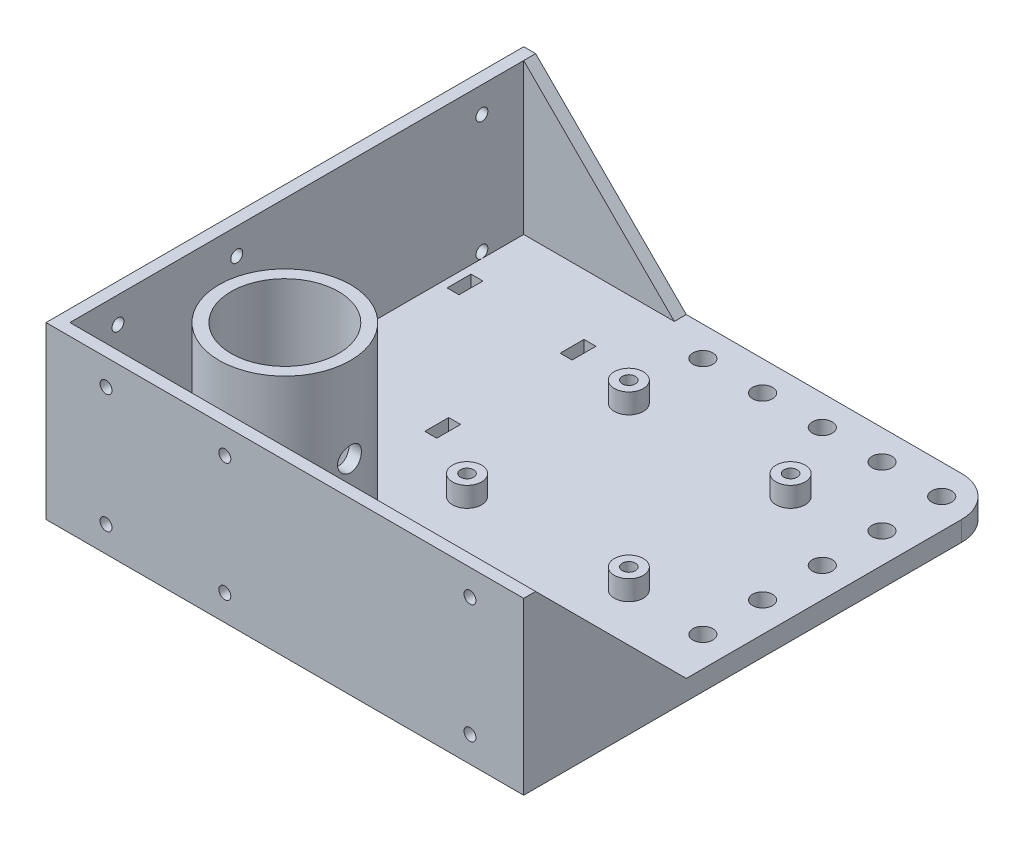
SolidWorks part; units mm, degrees
ref_plane "Front Plane" through (0, 0, 0) normal (0, 0, 1) x (1, 0, 0)
ref_plane "Top Plane" through (0, 0, 0) normal (0, 1, 0) x (1, 0, 0)
ref_plane "Right Plane" through (0, 0, 0) normal (1, 0, 0) x (0, 0, -1)
sketch "Sketch1" plane through (0, 0, 0) normal (0, 1, 0) x (1, 0, 0)
  line L0 (-30, -30) -> (90, 90) construction
  line L1 (-30, -30) -> (90, -30)
  line L2 (-30, -30) -> (-30, 90)
  line L3 (-30, 90) -> (90, 90)
  line L4 (90, -30) -> (90, 90)
  dimension "D1" = 120
  dimension "D2" = 30
extrude "Boss-Extrude1" add sketch "Sketch1" against normal blind 5
sketch "Sketch2" plane through (0, 0, 0) normal (0, 1, 0) x (1, 0, 0)
  line L0 (-30, 90) -> (-27, 90)
  line L1 (90, 90) -> (-30, 90) construction
  line L2 (-27, 90) -> (-27, -27)
  line L3 (-27, -27) -> (90, -27)
  line L4 (90, -30) -> (90, 90) construction
  line L5 (90, -27) -> (90, -30)
  line L6 (90, -30) -> (-30, -30)
  line L7 (-30, -30) -> (-30, 90)
  dimension "D1" = 3
extrude "Boss-Extrude2" add sketch "Sketch2" along normal blind 42.84 from surface starting at face at (30, -5, -30)
sketch "Sketch6" plane through (0, 0, 30) normal (0, 0, 1) x (1, 0, 0)
  line L0 (-14.92, 31.34) -> (14.92, 1.5) construction
  line L1 (14.92, 31.34) -> (-14.92, 1.5) construction
  line L2 (-30, -5) -> (-30, 37.84) construction
  line L3 (90, 37.84) -> (-30, 37.84) construction
  circle A0 centre (-14.92, 31.34) radius 1.5
  circle A1 centre (14.92, 31.34) radius 1.5
  circle A2 centre (14.92, 1.5) radius 1.5
  circle A3 centre (-14.92, 1.5) radius 1.5
  circle A4 centre (76.5, 31.34) radius 1.5
  circle A5 centre (76.5, 1.5) radius 1.5
  point P4 (0, 16.42)
  point P8 (-30, 16.42)
  dimension "D3" = 3
  dimension "D1" = 42.2
  dimension "D2" = 45
  dimension "D4" = 61.58
extrude "Cut-Extrude1" cut sketch "Sketch6" against normal through all
ref_plane "Plane1" through (0, 0, 0) normal (-0.7071, 0, -0.7071) x (-0.7071, 0, 0.7071)
mirror "Mirror1" about plane through (0, 0, 0) normal (-0.7071, 0, -0.7071) of "Cut-Extrude1"
sketch "Sketch3" plane through (90, 0, 0) normal (1, 0, 0) x (0, 0, -1)
  line L0 (-27, 37.84) -> (-27, 0)
  line L1 (-27, 0) -> (10.84, 0)
  line L2 (-27, 0) -> (90, 0) construction
  line L3 (10.84, 0) -> (-27, 37.84)
extrude "Boss-Extrude3" add sketch "Sketch3" against normal blind 3
sketch "Sketch7" plane through (0, 0, 0) normal (0, 1, 0) x (1, 0, 0)
  circle A0 centre (0, 0) radius 13.5
  dimension "D1" = 27
extrude "Cut-Extrude2" cut sketch "Sketch7" against normal through all
sketch "Sketch8" plane through (0, 0, 0) normal (0, 1, 0) x (1, 0, 0)
  circle A0 centre (0, 0) radius 13.5 construction
  circle A1 centre (0, 0) radius 13.5
  circle A2 centre (0, 0) radius 16.5
  dimension "D1" = 3
extrude "Boss-Extrude5" add sketch "Sketch8" along normal through all
sketch "Sketch9" plane through (0, 0, 0) normal (1, 0, 0) x (0, 0, -1)
  line L0 (0, 37.84) -> (0, -5) construction
  line L1 (13.5, 37.84) -> (-13.5, 37.84) construction
  line L2 (-30, -5) -> (90, -5) construction
  circle A0 centre (0, 16.42) radius 3
  dimension "D1" = 6
extrude "Cut-Extrude3" cut sketch "Sketch9" along normal through all
sketch "Sketch10" plane through (0, 0, 0) normal (0, 1, 0) x (1, 0, 0)
  line L0 (37.75, 3.4) -> (65.75, -22) construction
  line L5 (31.75, 3.4) -> (37.75, 3.4)
  line L6 (31.75, 3.4) -> (31.75, 6.4)
  line L7 (31.75, 6.4) -> (37.75, 6.4)
  line L8 (37.75, 3.4) -> (37.75, 6.4)
  line L9 (71.75, 3.4) -> (65.75, 3.4)
  line L10 (71.75, 3.4) -> (71.75, 6.4)
  line L11 (71.75, 6.4) -> (65.75, 6.4)
  line L12 (65.75, 3.4) -> (65.75, 6.4)
  line L13 (71.75, -22) -> (65.75, -22)
  line L14 (71.75, -22) -> (71.75, -25)
  line L15 (71.75, -25) -> (65.75, -25)
  line L16 (65.75, -22) -> (65.75, -25)
  line L17 (31.75, -22) -> (37.75, -22)
  line L18 (31.75, -22) -> (31.75, -25)
  line L19 (31.75, -25) -> (37.75, -25)
  line L20 (37.75, -22) -> (37.75, -25)
  line L21 (21.75, 3.4) -> (81.75, 3.4) construction
  line L22 (21.75, 3.4) -> (21.75, -22) construction
  line L23 (21.75, -22) -> (81.75, -22) construction
  line L24 (81.75, 3.4) -> (81.75, -22) construction
  line L25 (-27, -27) -> (87, -27) construction
  line L27 (16.5, 0) -> (21.75, 0) construction
  line L28 (81.75, -9.3) -> (87, -9.3) construction
  line L29 (87, 10.84) -> (87, -27) construction
  line L30 (90, 90) -> (-30, -30) construction
  line L31 (90, 10.84) -> (90, 90) construction
  circle A0 centre (0, 0) radius 16.5 construction
  circle A1 centre (0, 0) radius 16.5 construction
  circle A2 centre (82.5, 82.5) radius 2.5
  circle A3 centre (82.5, 67.5) radius 2.5
  circle A4 centre (82.5, 52.5) radius 2.5
  circle A5 centre (82.5, 37.5) radius 2.5
  circle A6 centre (82.5, 22.5) radius 2.5
  point P20 (51.75, -9.3)
  point P21 (51.75, 3.4)
  dimension "D8" = 5
  dimension "D1" = 3
  dimension "D2" = 6
  dimension "D3" = 10
  dimension "D4" = 60
  dimension "D5" = 2
  dimension "D6" = 7.5
  dimension "D7" = 25.4
  dimension "D9" = 15
extrude "Cut-Extrude4" cut sketch "Sketch10" against normal through all
mirror "Mirror2" about plane through (0, 0, 0) normal (-0.7071, 0, -0.7071) of "Cut-Extrude4", "Boss-Extrude3", "Cut-Extrude3"
fillet "Fillet1" radius 10 1 edges at (90, -2.5, -90)
sketch "Sketch11" plane through (0, 0, 0) normal (0, 1, 0) x (1, 0, 0)
  line L0 (34.75, 6.4) -> (34.75, 17.8) construction
  line L1 (17.8, 17.8) -> (68.6, 17.8) construction
  line L2 (17.8, 17.8) -> (17.8, 68.6) construction
  line L3 (17.8, 68.6) -> (68.6, 68.6) construction
  line L4 (68.6, 17.8) -> (68.6, 68.6) construction
  line L5 (22.88, 22.88) -> (22.88, 63.52) construction
  line L6 (22.88, 63.52) -> (63.52, 63.52) construction
  line L7 (37.75, 6.4) -> (31.75, 6.4) construction
  line L8 (6.4, 31.75) -> (17.8, 31.75) construction
  line L9 (37.5, 80) -> (37.5, 68.6) construction
  line L10 (80, 37.5) -> (68.6, 37.5) construction
  line L19 (63.52, 22.88) -> (63.52, 63.52) construction
  line L20 (22.88, 22.88) -> (63.52, 22.88) construction
  circle A0 centre (22.88, 63.52) radius 1.65
  circle A1 centre (37.5, 82.5) radius 2.5 construction
  circle A2 centre (82.5, 37.5) radius 2.5 construction
  circle A4 centre (63.52, 63.52) radius 1.65
  circle A5 centre (63.52, 22.88) radius 1.65
  circle A6 centre (22.88, 22.88) radius 1.65
  dimension "D3" = 3.3
  dimension "D1" = 50.8
  dimension "D2" = 5.08
extrude "Cut-Extrude5" cut sketch "Sketch11" against normal through all
sketch "Sketch12" plane through (0, 0, 0) normal (0, 1, 0) x (1, 0, 0)
  circle A0 centre (22.88, 22.88) radius 1.65 construction
  circle A1 centre (63.52, 22.88) radius 1.65 construction
  circle A2 centre (63.52, 63.52) radius 1.65 construction
  circle A3 centre (22.88, 63.52) radius 1.65 construction
  circle A4 centre (22.88, 22.88) radius 1.65
  circle A5 centre (63.52, 22.88) radius 1.65
  circle A6 centre (63.52, 63.52) radius 1.65
  circle A7 centre (22.88, 63.52) radius 1.65
  circle A8 centre (22.88, 63.52) radius 3.65
  circle A9 centre (63.52, 63.52) radius 3.65
  circle A10 centre (63.52, 22.88) radius 3.65
  circle A11 centre (22.88, 22.88) radius 3.65
  dimension "D1" = 2
extrude "Boss-Extrude6" add sketch "Sketch12" along normal blind 5
chamfer "Chamfer1" distance 2.5 angle 45 4 edges at (63.52, -5, -21.23) (63.52, -5, -61.87) (22.88, -5, -61.87) (22.88, -5, -21.23)
